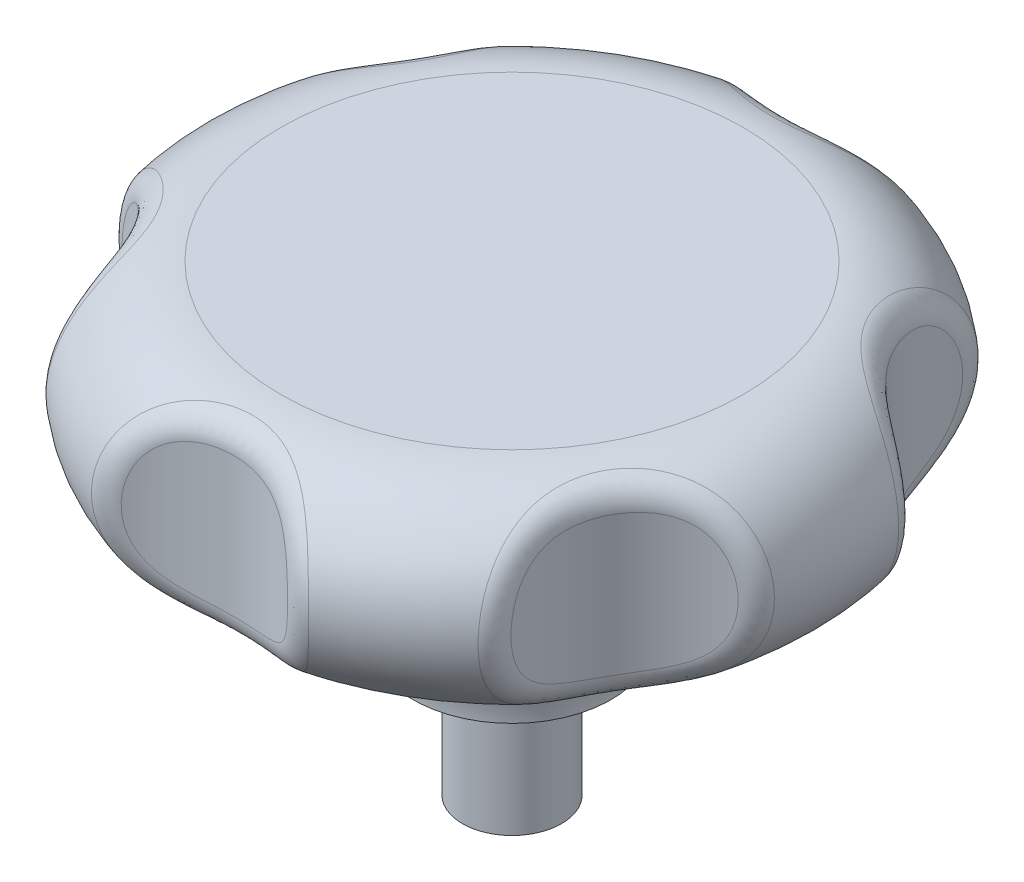
SolidWorks part; units mm, degrees
ref_plane "Front" through (0, 0, 0) normal (0, 0, 1) x (1, 0, 0)
ref_plane "Top" through (0, 0, 0) normal (0, 1, 0) x (-1, 0, 0)
ref_plane "Right" through (0, 0, 0) normal (1, 0, 0) x (0, 0, -1)
sketch "Sketch1" plane through (0, 0, 0) normal (0, 0, 1) x (1, 0, 0)
  line L0 (0, 0) -> (0, 36.2882) construction
  line L1 (0, 0) -> (0, 22.225)
  line L2 (0, 22.225) -> (11.1125, 22.225)
  line L4 (4.7625, 6.35) -> (2.3813, 6.35)
  line L5 (2.3813, 6.35) -> (2.3812, 0)
  line L6 (2.3812, 0) -> (0, 0)
  arc A0 (11.1125, 22.225) -> (11.1125, 12.7) centre (11.1125, 17.4625) cw
  arc A1 (11.1125, 12.7) -> (4.7625, 6.35) centre (11.1125, 6.35) ccw
  dimension "D5" = 6.35
  dimension "D6" = 4.7625
  dimension "D1" = 2.3813
  dimension "D2" = 4.7625
  dimension "D3" = 6.35
  dimension "D4" = 15.875
revolve "Base-Revolve" add sketch "Sketch1" angle 360 about L0
sketch "Sketch2" plane through (0, 22.225, 0) normal (0, 1, 0) x (1, 0, 0)
  line L0 (0, 0) -> (0, 19.7169) construction
  line L1 (0, 19.7169) -> (-4.4901, 15.2268)
  line L2 (4.4901, 15.2268) -> (0, 19.7169)
  circle A1 centre (0, 0) radius 15.875 construction
  arc A2 (-4.4901, 15.2268) -> (4.4901, 15.2268) centre (0, 19.7169) ccw
  dimension "D1" = 6.35
  dimension "D2" = 90
extrude "Cut-Extrude1" cut sketch "Sketch2" against normal through all
pattern_circular "CirPattern1" count 6 over 360 of "Cut-Extrude1"
fillet "Fillet1" radius 1.27 6 edges at (13.7566, 20.8532, -4.4447) (-14.6541, 19.928, -3.9882) (2.4719, 21.1824, -13.8678) (11.226, 21.6184, 7.3871) (3.6462, 20.257, 14.5181) (-10.7466, 20.2979, 10.3772)
